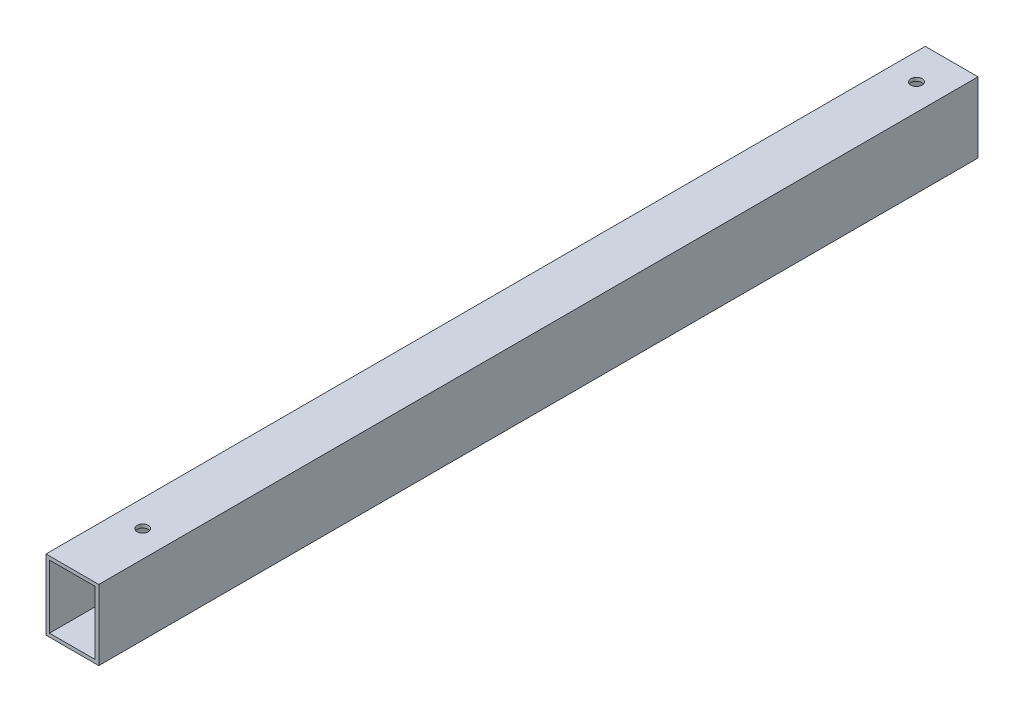
SolidWorks part; units mm, degrees
material "1060 合金"
ref_plane "前视基准面" through (0, 0, 0) normal (0, 0, 1) x (1, 0, 0)
ref_plane "上视基准面" through (0, 0, 0) normal (0, 1, 0) x (1, 0, 0)
ref_plane "右视基准面" through (0, 0, 0) normal (1, 0, 0) x (0, 0, -1)
other "Configuration Table"
sketch "草图1" plane through (0, 0, 0) normal (0, 0, 1) x (1, 0, 0)
  line L1 (0, 0) -> (15, 0)
  line L2 (0, 0) -> (0, -20)
  line L3 (0, -20) -> (15, -20)
  line L4 (15, 0) -> (15, -20)
  dimension "D1" = 20
  dimension "D2" = 15
extrude "拉伸-薄壁1" add sketch "草图1" along normal blind 250 thin thin type one direction reverse wall 1
sketch "草图2" plane through (0, -20, 0) normal (0, -1, 0) x (1, 0, 0)
  circle A1 centre (7.5, 825) radius 2.6
  circle A2 centre (7.5, 825) radius 2.6
  dimension "D1" = 0
extrude "切除-拉伸1" [suppressed] cut sketch "草图2" against normal up to next
sketch "草图3" plane through (0, 0, 0) normal (0, 1, 0) x (1, 0, 0)
  line L0 (15, -250) -> (15, 0) construction
  line L1 (15, 0) -> (0, 0) construction
  circle A0 centre (7.5, -10) radius 1.6
  circle A1 centre (7.5, -230) radius 1.6
  dimension "D3" = 3.2
  dimension "D1" = 7.5
  dimension "D2" = 10
  dimension "D4" = 2
extrude "切除-拉伸2" cut sketch "草图3" against normal through all
